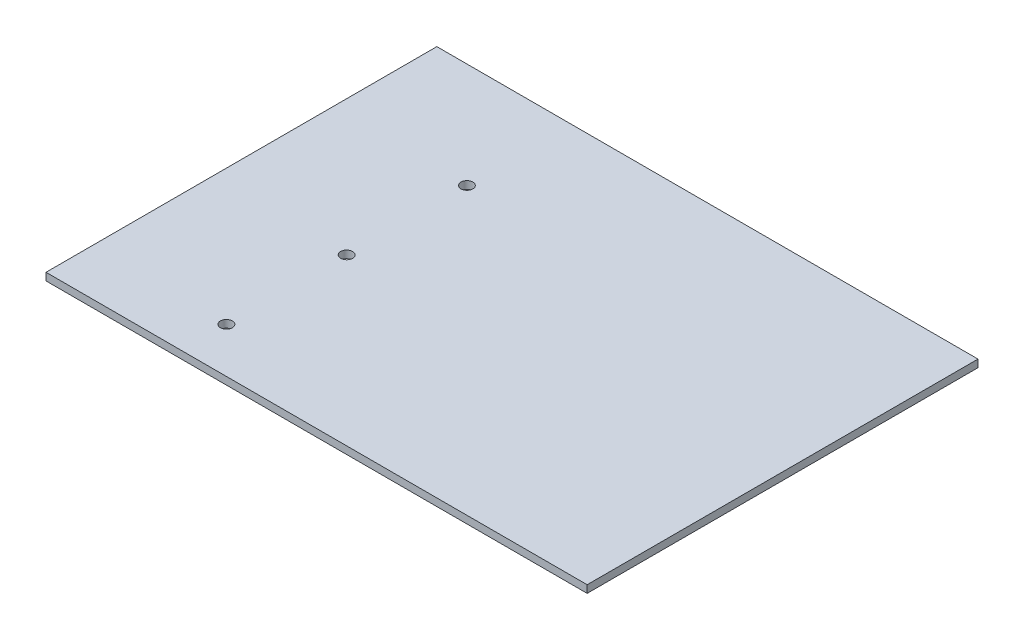
SolidWorks part; units mm, degrees
material "ASTM A36 Steel"
ref_plane "Front Plane" through (0, 0, 0) normal (0, 0, 1) x (1, 0, 0)
ref_plane "Top Plane" through (0, 0, 0) normal (0, 1, 0) x (1, 0, 0)
ref_plane "Right Plane" through (0, 0, 0) normal (1, 0, 0) x (0, 0, -1)
sketch "Sketch1" plane through (0, 0, 0) normal (0, 1, 0) x (1, 0, 0)
  line L1 (-228.6, 165.1) -> (228.6, 165.1)
  line L2 (-228.6, 165.1) -> (-228.6, -165.1)
  line L3 (-228.6, -165.1) -> (228.6, -165.1)
  line L4 (228.6, 165.1) -> (228.6, -165.1)
  dimension "D1" = 330.2
  dimension "D2" = 457.2
  dimension "D3" = 165.1
  dimension "D4" = 228.6
extrude "Boss-Extrude1" add sketch "Sketch1" along normal blind 6.35
sketch "Sketch3" plane through (0, 0, 0) normal (0, -1, 0) x (1, 0, 0)
  line L0 (-203.2, -61.3833) -> (203.2, -61.3833)
  line L1 (-228.6, 165.1) -> (228.6, 165.1)
  line L2 (-228.6, 165.1) -> (-228.6, -165.1)
  line L3 (-228.6, -165.1) -> (228.6, -165.1) construction
  line L4 (228.6, 165.1) -> (228.6, -165.1)
  line L5 (-150.5857, 139.7) -> (-144.2357, 139.7)
  line L6 (-150.5857, 139.7) -> (-150.5857, -165.1)
  line L7 (-150.5857, -165.1) -> (-144.2357, -165.1)
  line L8 (-144.2357, 139.7) -> (-144.2357, -165.1)
  line L9 (-203.2, -165.1) -> (203.2, -165.1)
  line L10 (-203.2, -165.1) -> (-203.2, 139.7)
  line L11 (-203.2, 139.7) -> (203.2, 139.7)
  line L12 (203.2, -165.1) -> (203.2, 139.7)
  line L13 (-203.2, 42.3333) -> (203.2, 42.3333)
  line L14 (-203.2, 42.3333) -> (-203.2, 35.9833)
  line L15 (-203.2, 35.9833) -> (203.2, 35.9833)
  line L16 (203.2, 42.3333) -> (203.2, 35.9833)
  line L17 (-203.2, -61.3833) -> (-203.2, -67.7333)
  line L18 (-203.2, -67.7333) -> (203.2, -67.7333)
  line L19 (203.2, -61.3833) -> (203.2, -67.7333)
  line L20 (-203.2, -171.45) -> (203.2, -171.45)
  line L21 (-203.2, -171.45) -> (-203.2, -165.1)
  line L22 (-203.2, -165.1) -> (203.2, -165.1)
  line L23 (203.2, -171.45) -> (203.2, -165.1)
  line L24 (228.6, -165.1) -> (-228.6, -165.1) construction
  line L25 (-91.6214, 139.7) -> (-85.2714, 139.7)
  line L26 (-91.6214, 139.7) -> (-91.6214, -165.1)
  line L27 (-91.6214, -165.1) -> (-85.2714, -165.1)
  line L28 (-85.2714, 139.7) -> (-85.2714, -165.1)
  line L29 (-32.6571, 139.7) -> (-26.3071, 139.7)
  line L30 (-32.6571, 139.7) -> (-32.6571, -165.1)
  line L31 (-32.6571, -165.1) -> (-26.3071, -165.1)
  line L32 (-26.3071, 139.7) -> (-26.3071, -165.1)
  line L33 (26.3071, 139.7) -> (32.6571, 139.7)
  line L34 (26.3071, 139.7) -> (26.3071, -165.1)
  line L35 (26.3071, -165.1) -> (32.6571, -165.1)
  line L36 (32.6571, 139.7) -> (32.6571, -165.1)
  line L37 (85.2714, 139.7) -> (91.6214, 139.7)
  line L38 (85.2714, 139.7) -> (85.2714, -165.1)
  line L39 (85.2714, -165.1) -> (91.6214, -165.1)
  line L40 (91.6214, 139.7) -> (91.6214, -165.1)
  line L42 (203.2, 139.7) -> (203.2, -165.1)
  line L43 (144.2357, 139.7) -> (150.5857, 139.7)
  line L44 (144.2357, 139.7) -> (144.2357, -165.1)
  line L45 (144.2357, -165.1) -> (150.5857, -165.1)
  line L46 (150.5857, 139.7) -> (150.5857, -165.1)
  text T0 "LOL HOW DO LINEAR PATTERNS WORK ON THIS THING"
  dimension "D1" = 6.35
  dimension "D2" = 25.4
  dimension "D3" = 25.4
  dimension "D4" = 25.4
  dimension "D5" = 6.35
  dimension "D6" = 103.7167
  dimension "D7" = 6.35
  dimension "D8" = 6.35
  dimension "D9" = 103.7167
  dimension "D10" = 103.7167
  dimension "D11" = 58.9643
  dimension "D12" = 6.35
  dimension "D13" = 6.35
  dimension "D14" = 6.35
  dimension "D15" = 6.35
  dimension "D16" = 6.35
  dimension "D17" = 58.9643
  dimension "D18" = 58.9643
  dimension "D19" = 58.9643
  dimension "D20" = 58.9643
  dimension "D21" = 58.9643
extrude "Boss-Extrude2" add sketch "Sketch3" along normal blind 25.4 contours L13 L16 L15 L14 | L0 L19 L18 L17 | L6 L7 L8 L5 | L26 L27 L28 L25 | L30 L31 L32 L29 | L34 L35 L36 L33 | L38 L39 L40 L37 | L44 L45 L46 L43
hole_wizard "3/8 Clearance Hole1" positions "Sketch4" profile "Sketch5" hole size "3/8" standard "ANSI Inch" end condition through all
sketch "Sketch4" plane through (0, 6.35, -165.1) normal (0, 1, 0) x (1, 0, 0)
  point P0 (-114.3, -88.9)
  point P1 (-114.3, -190.5)
  point P2 (-114.3, -292.1)
sketch "Sketch5" plane through (-114.3, 6.35, -76.2) normal (1, 0, 0) x (0, 0, 1)
  line L0 (0, 0) -> (0, 31.75)
  line L1 (0, 31.75) -> (5.0419, 31.75)
  line L2 (5.0419, 31.75) -> (5.0419, 0)
  line L5 (5.0419, 0) -> (0, 0)
  line L11 (0, -6.35) -> (0, 107.95) construction
  dimension "Thru Hole Dia." = 10.0838
  dimension "Thru Hole Depth" = 31.75
equation "\"Var1\"=13"
equation "\"D1@Sketch1\"=\"Var1\""
equation "\"Var2\"=18"
equation "\"D2@Sketch1\"=\"Var2\""
equation "\"D3@Sketch1\"=\"Var1\"/2"
equation "\"D4@Sketch1\"=\"Var2\"/2"
equation "\"D1@Sketch3\"=\"t\""
equation "\"t\"= 0.25"
equation "\"D5@Sketch3\"=\"t\""
equation "\"#H\"= 3"
equation "\"#V\"= 7"
equation "\"D6@Sketch3\"=\"DH\""
equation "\"DH\"= ( \"Var1\" - 1 + \"t\" ) / \"#H\""
equation "\"D7@Sketch3\"=\"t\""
equation "\"D8@Sketch3\"=\"t\""
equation "\"D9@Sketch3\"=\"DH\""
equation "\"D10@Sketch3\"=\"DH\""
equation "\"D11@Sketch3\"=\"DV\""
equation "\"DV\"= ( \"Var2\" + \"t\" - 2 ) / \"#V\""
equation "\"D12@Sketch3\"=\"t\""
equation "\"D13@Sketch3\"=\"t\""
equation "\"D14@Sketch3\"=\"t\""
equation "\"D15@Sketch3\"=\"t\""
equation "\"D17@Sketch3\"=\"DV\""
equation "\"D18@Sketch3\"=\"DV\""
equation "\"D19@Sketch3\"=\"DV\""
equation "\"D20@Sketch3\"=\"DV\""
equation "\"D16@Sketch3\"=\"t\""
equation "\"D21@Sketch3\"=\"DV\""
